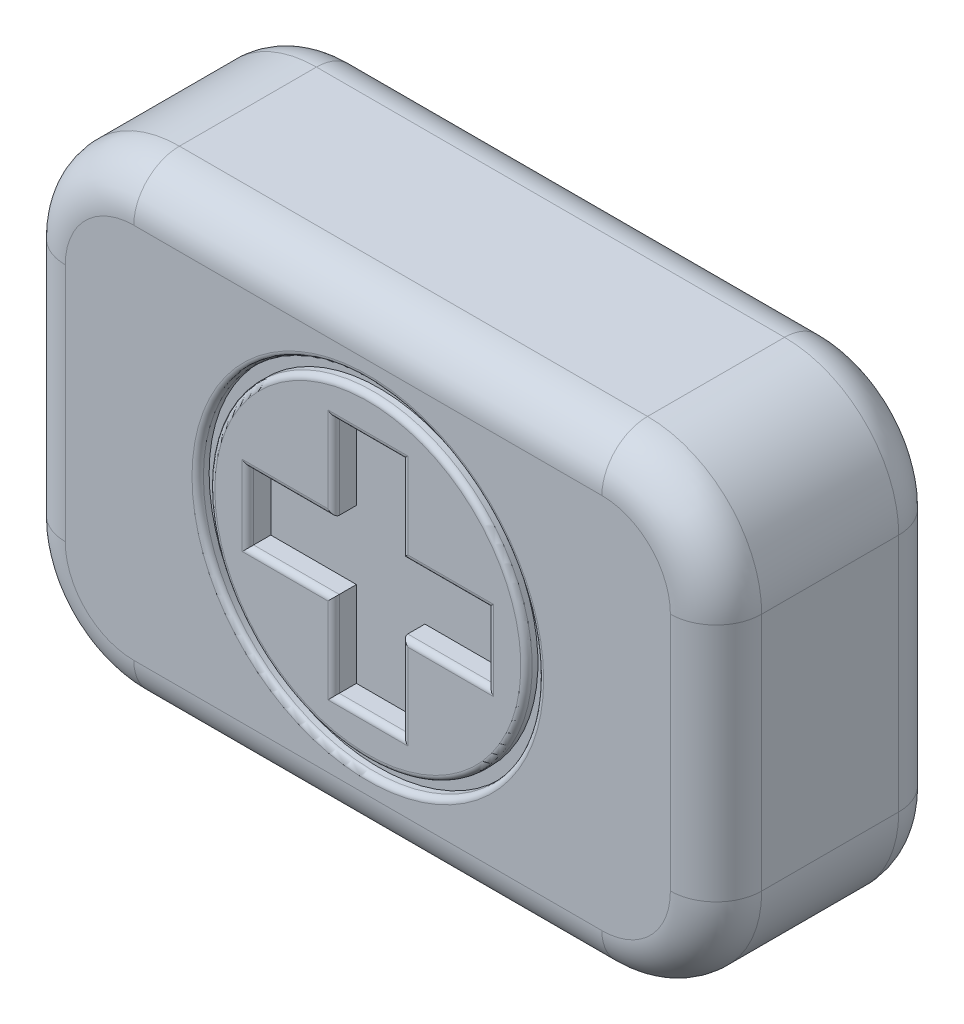
SolidWorks part; units mm, degrees
ref_plane "Front Plane" through (0, 0, 0) normal (0, 0, 1) x (1, 0, 0)
ref_plane "Top Plane" through (0, 0, 0) normal (0, 1, 0) x (1, 0, 0)
ref_plane "Right Plane" through (0, 0, 0) normal (1, 0, 0) x (0, 0, -1)
sketch "Sketch1" plane through (0, 0, 0) normal (0, 0, 1) x (1, 0, 0)
  line L1 (152.5, 102.5) -> (-152.5, 102.5)
  line L2 (152.5, 102.5) -> (152.5, -102.5)
  line L3 (152.5, -102.5) -> (-152.5, -102.5)
  line L4 (-152.5, 102.5) -> (-152.5, -102.5)
  line L5 (152.5, 102.5) -> (-152.5, -102.5) construction
  line L6 (152.5, -102.5) -> (-152.5, 102.5) construction
  point P0 (0, 0)
  dimension "D1" = 305
  dimension "D2" = 205
extrude "Boss-Extrude1" add sketch "Sketch1" along normal blind 100
fillet "Fillet1" radius 50 4 edges at (152.5, -102.5, 50) (-152.5, -102.5, 50) (-152.5, 102.5, 50) (152.5, 102.5, 50)
fillet "Fillet2" radius 20 16 edges at (-152.5, 0, 0) (-137.8553, -87.8553, 0) (0, -102.5, 0) (137.8553, -87.8553, 0) (152.5, 0, 0) (137.8553, 87.8553, 0) (0, 102.5, 0) (137.8553, 87.8553, 100) (152.5, 0, 100) (137.8553, -87.8553, 100) (0, -102.5, 100) (-137.8553, -87.8553, 100) (-152.5, 0, 100) (-137.8553, 87.8553, 100) (-137.8553, 87.8553, 0) (0, 102.5, 100)
sketch "Sketch2" plane through (0, 0, 0) normal (0, 0, 1) x (1, 0, 0)
  line L0 (0, 52.5) -> (0, -52.5)
  line L1 (-52.5, 0) -> (52.5, 0)
  circle A0 centre (0, 0) radius 72
  point P5 (0, 0)
  point P7 (0, 0)
  dimension "D2" = 144
  dimension "D1" = 105
extrude "Cut-Extrude-Thin1" cut sketch "Sketch2" along normal blind 10 thin contours L0 | L1 thin type mid plane wall 30
extrude "Cut-Extrude-Thin2" cut sketch "Sketch2<3>" against normal blind 10 from surface thin contours L0 | L1 starting at face at (0, 0, 100) thin type mid plane wall 30
sketch "Sketch2<3>" plane through (0, 0, 0) normal (0, 0, 1) x (1, 0, 0) same geometry as "Sketch2"
extrude "Cut-Extrude-Thin3" cut sketch "Sketch2<4>" along normal blind 5 thin contours A0 thin type mid plane wall 5
sketch "Sketch2<4>" plane through (0, 0, 0) normal (0, 0, 1) x (1, 0, 0) same geometry as "Sketch2"
extrude "Cut-Extrude-Thin4" cut sketch "Sketch2<5>" against normal blind 5 from surface thin contours A0 starting at face at (0, 0, 100) thin type mid plane wall 5
sketch "Sketch2<5>" plane through (0, 0, 0) normal (0, 0, 1) x (1, 0, 0) same geometry as "Sketch2"
fillet "Fillet3" radius 2.5 28 edges at (69.5, 0, 0) (74.5, 0, 0) (0, 52.5, 0) (-15, 33.75, 0) (-33.75, 15, 0) (-52.5, 0, 0) (-33.75, -15, 0) (-15, -33.75, 0) (0, -52.5, 0) (15, -33.75, 0) (33.75, -15, 0) (52.5, 0, 0) (33.75, 15, 0) (15, 33.75, 0) (52.5, 0, 100) (33.75, 15, 100) (33.75, -15, 100) (15, -33.75, 100) (0, -52.5, 100) (-15, -33.75, 100) (-33.75, -15, 100) (-52.5, 0, 100) (-33.75, 15, 100) (-15, 33.75, 100) (0, 52.5, 100) (15, 33.75, 100) (-69.5, 0, 100) (-74.5, 0, 100)
